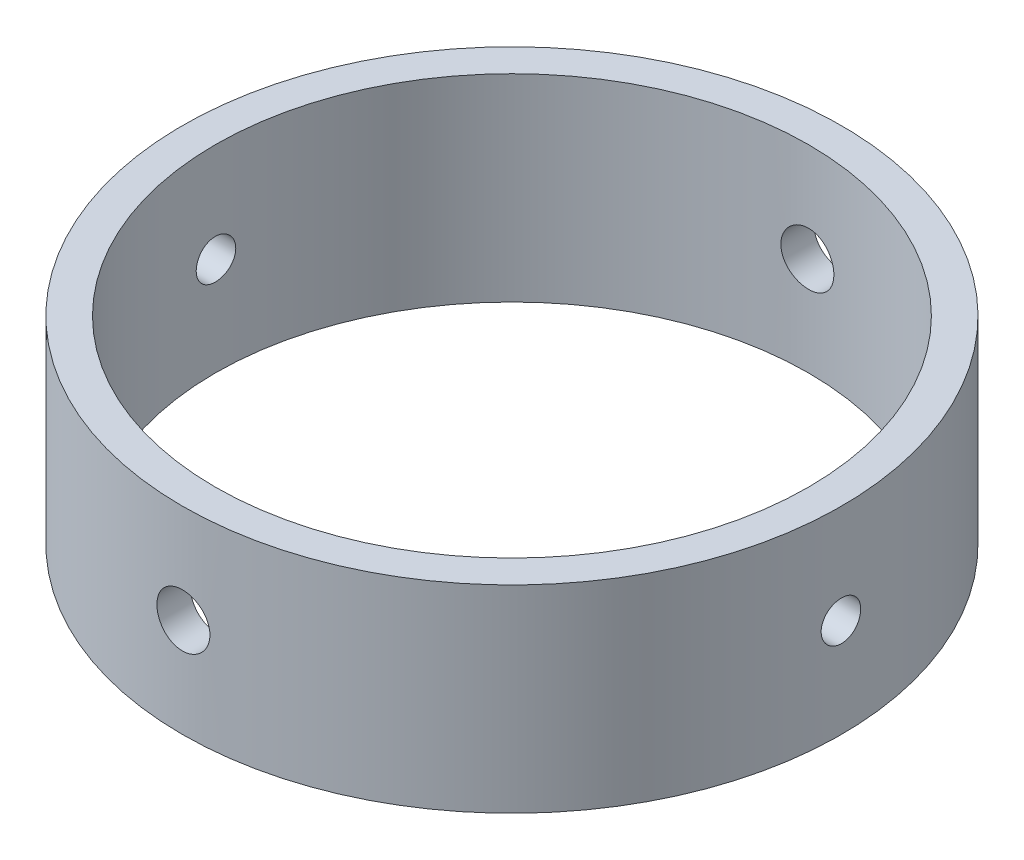
SolidWorks part; units mm, degrees
ref_plane "Front Plane" through (0, 0, 0) normal (0, 0, 1) x (1, 0, 0)
ref_plane "Top Plane" through (0, 0, 0) normal (0, 1, 0) x (1, 0, 0)
ref_plane "Right Plane" through (0, 0, 0) normal (1, 0, 0) x (0, 0, -1)
sketch "Sketch1" plane through (0, 0, 0) normal (0, 1, 0) x (1, 0, 0)
  circle A0 centre (0, 0) radius 31.75
  circle A1 centre (0, 0) radius 28.575
  dimension "D1" = 63.5
  dimension "D2" = 57.15
extrude "Boss-Extrude1" add sketch "Sketch1" along normal blind 19.05
ref_plane "Plane1" through (0, 0, 31.75) normal (0, 0, 1) x (1, 0, 0)
ref_plane "Plane2" through (0, 0, -31.75) normal (0, 0, 1) x (1, 0, 0)
sketch "Sketch3" plane through (0, 0, 31.75) normal (0, 0, 1) x (1, 0, 0)
  line L0 (28.575, 19.05) -> (-28.575, 19.05) construction
  circle A0 centre (0, 9.525) radius 2.7224
  dimension "D1" = 9.525
hole_wizard "Tap Drill for 1/4-20 Tap1" positions "Sketch4" profile "Sketch5" hole size "1/4-20" standard "ANSI Inch" end condition up to next
sketch "Sketch4" plane through (0, 0, 31.75) normal (0, 0, 1) x (1, 0, 0)
  point P0 (0, 9.525)
sketch "Sketch5" plane through (0, 9.525, 31.75) normal (1, 0, 0) x (0, -1, 0)
  line L0 (0, 0) -> (0, 3.175)
  line L1 (0, 3.175) -> (2.5527, 3.175)
  line L2 (2.5527, 3.175) -> (2.5527, 0)
  line L5 (2.5527, 0) -> (0, 0)
  line L11 (0, -6.35) -> (0, 107.95) construction
  dimension "Thru Hole Dia." = 5.1054
  dimension "Thru Hole Depth" = 3.175
sketch "Sketch7" plane through (0, 0, -31.75) normal (0, 0, 1) x (1, 0, 0)
  line L0 (31.75, 19.05) -> (-31.75, 19.05) construction
  circle A0 centre (0, 9.525) radius 3.5632
  dimension "D1" = 9.525
hole_wizard "Tap Drill for 1/4-20 Tap2" positions "Sketch8" profile "Sketch9" hole size "1/4-20" standard "ANSI Inch" end condition up to next
sketch "Sketch8" plane through (0, 0, -31.75) normal (0, 0, 1) x (1, 0, 0)
  point P0 (0, 9.525)
sketch "Sketch9" plane through (0, 9.525, -31.75) normal (1, 0, 0) x (0, 1, 0)
  line L0 (0, 0) -> (0, 3.175)
  line L1 (0, 3.175) -> (2.5527, 3.175)
  line L2 (2.5527, 3.175) -> (2.5527, 0)
  line L5 (2.5527, 0) -> (0, 0)
  line L11 (0, -6.35) -> (0, 107.95) construction
  dimension "Thru Hole Dia." = 5.1054
  dimension "Thru Hole Depth" = 3.175
ref_plane "Plane3" through (31.75, 0, 0) normal (1, 0, 0) x (0, 0, -1)
ref_plane "Plane4" through (-31.75, 0, 0) normal (1, 0, 0) x (0, 0, -1)
sketch "Sketch10" plane through (-31.75, 0, 0) normal (1, 0, 0) x (0, 0, -1)
  circle A0 centre (0, 9.4879) radius 1.905
  dimension "D1" = 3.81
extrude "Cut-Extrude3" cut sketch "Sketch10" against normal through all and the other way through all
